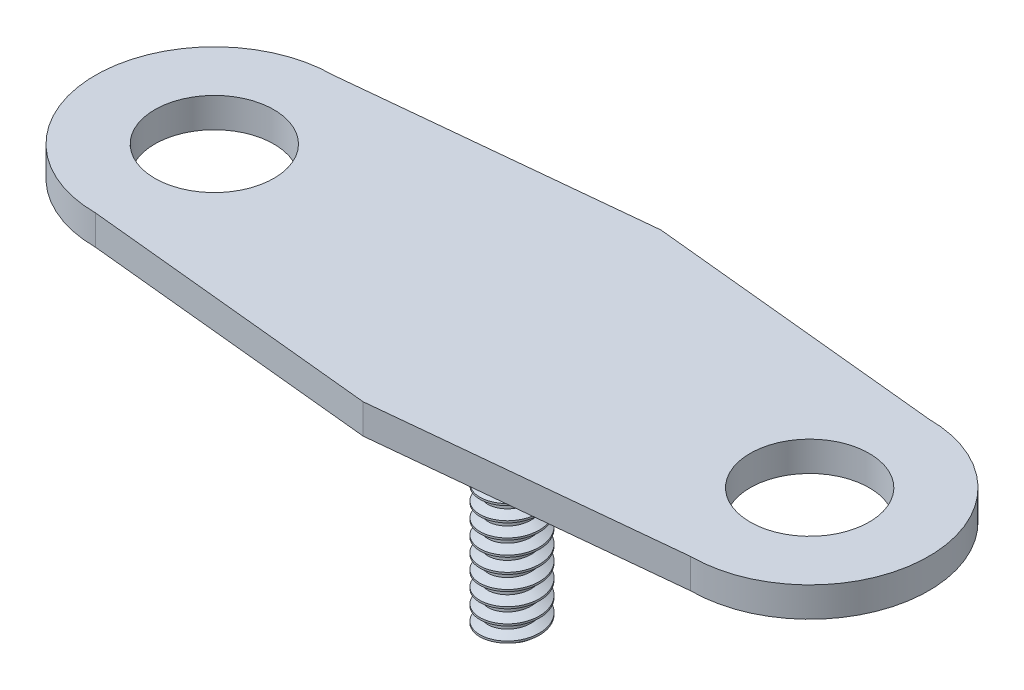
SolidWorks part; units mm, degrees
ref_plane "Front Plane" through (0, 0, 0) normal (0, 0, 1) x (1, 0, 0)
ref_plane "Top Plane" through (0, 0, 0) normal (0, 1, 0) x (1, 0, 0)
ref_plane "Right Plane" through (0, 0, 0) normal (1, 0, 0) x (0, 0, -1)
sketch "Sketch1" plane through (0, 0, 0) normal (0, 1, 0) x (1, 0, 0)
  circle A0 centre (0, 0) radius 0.5
extrude "Boss-Extrude1" add sketch "Sketch1" along normal blind 4
thread "Thread1" pitch 0.25 method cut profile "Thread Profile1" start angle 0, offset 0, length 4, pitch 0.25, diameter 1
ref_plane "Plane1" through (-0.5, 4, 0) normal (0, 0, 1) x (-1, 0, 0)
sketch "Thread Profile1" plane through (-0.5, 4, 0) normal (0, 0, 1) x (-1, 0, 0)
  line L0 (0, 0) -> (0, 0.25) construction
  line L11 (0, 0) -> (0, 0.2187)
  line L12 (0, 0.2187) -> (-0.1353, 0.1406)
  line L13 (-0.1353, 0.1406) -> (-0.1353, 0.0781)
  line L15 (-0.1353, 0.0781) -> (0, 0)
  line L17 (-0.1353, 0.1094) -> (0, 0.1094) construction
  point P2 (0, 0)
  dimension "Pitch" = 0.25
  dimension "Profile_Angle" = 60
  dimension "Profile_Land" = 0.0625
  dimension "Profile_Height" = 0.1353
sketch "Sketch2" plane through (0, 4, 0) normal (0, 1, 0) x (1, 0, 0)
  line L0 (0, 0) -> (5, 0)
  line L1 (0, 0) -> (-5, 0)
  line L8 (0, 2.5) -> (5, 2)
  line L9 (0, 2.5) -> (-5, 2)
  line L10 (-5, -2) -> (0, -2.5)
  line L11 (0, -2.5) -> (5, -2)
  arc A3 (0.495, 2.4505) -> (-0.495, 2.4505) centre (0, 0) ccw
  arc A6 (5, -2) -> (5, 2) centre (5, 0) ccw
  arc A7 (-5, 2) -> (-5, -2) centre (-5, 0) ccw
  arc A8 (-0.495, -2.4505) -> (0.495, -2.4505) centre (0, 0) ccw
  circle A9 centre (-5, 0) radius 1
  circle A10 centre (5, 0) radius 1
extrude "Boss-Extrude2" add sketch "Sketch2" along normal blind 0.5
